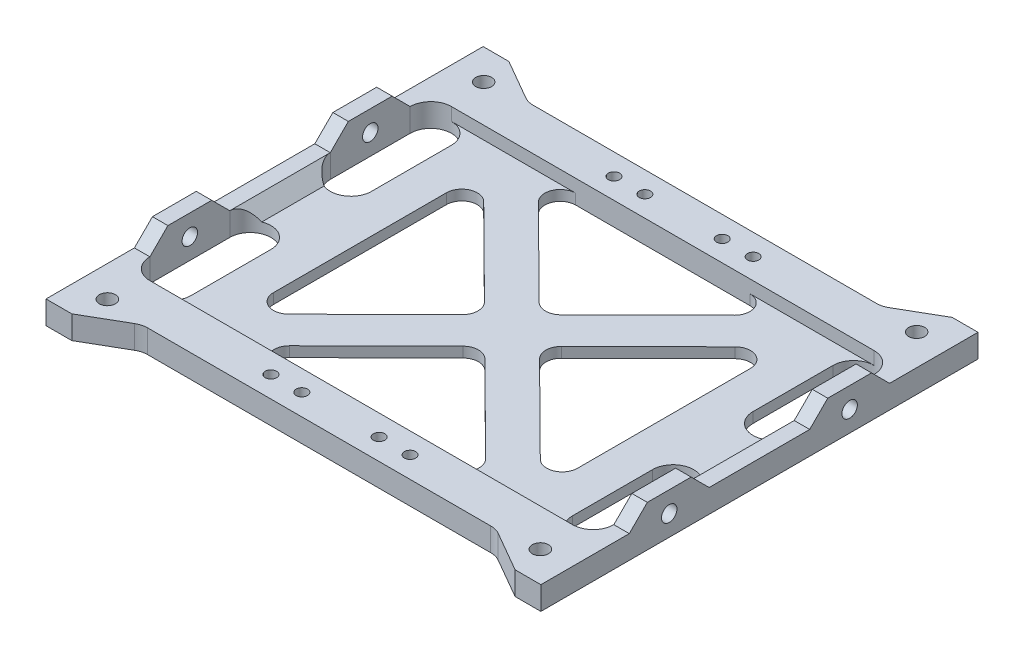
SolidWorks part; units mm, degrees
material "6061-T6 (SS)"
ref_plane "Front Plane" through (0, 0, 0) normal (0, 0, 1) x (1, 0, 0)
ref_plane "Top Plane" through (0, 0, 0) normal (0, 1, 0) x (1, 0, 0)
ref_plane "Right Plane" through (0, 0, 0) normal (1, 0, 0) x (0, 0, -1)
sketch "Sketch1" plane through (0, 0, 0) normal (0, 1, 0) x (1, 0, 0)
  line L0 (-41, 25.25) -> (-41, 9.75) construction
  line L1 (-48, -42.4) -> (-43, -42.4)
  line L2 (-48, -42.4) -> (-48, 42.4)
  line L3 (-48, 42.4) -> (-43, 42.4)
  line L4 (48, -42.4) -> (48, 42.4)
  line L5 (-48, -42.4) -> (48, 42.4) construction
  line L6 (-48, 42.4) -> (48, -42.4) construction
  line L7 (-37, 25.25) -> (-37, 9.75)
  line L8 (-45, 25.25) -> (-45, 9.75)
  line L9 (-41, -9.75) -> (-41, -25.25) construction
  line L10 (-37, -9.75) -> (-37, -25.25)
  line L11 (-45, -9.75) -> (-45, -25.25)
  line L12 (41, 25.25) -> (41, 9.75) construction
  line L13 (45, 25.25) -> (45, 9.75)
  line L14 (37, 25.25) -> (37, 9.75)
  line L15 (41, -9.75) -> (41, -25.25) construction
  line L16 (45, -9.75) -> (45, -25.25)
  line L17 (37, -9.75) -> (37, -25.25)
  line L18 (-43, -42.4) -> (-35.2679, -37.9359)
  line L19 (-33.2679, -37.4) -> (33.2679, -37.4)
  line L20 (35.2679, -37.9359) -> (43, -42.4)
  line L21 (43, 42.4) -> (35.2679, 37.9359)
  line L22 (33.2679, 37.4) -> (-33.2679, 37.4)
  line L23 (-35.2679, 37.9359) -> (-43, 42.4)
  line L24 (43, -42.4) -> (48, -42.4)
  line L25 (43, 42.4) -> (48, 42.4)
  line L26 (-37.6698, 33.275) -> (37.6698, 33.275) construction
  line L27 (37.6698, -33.275) -> (-37.6698, -33.275) construction
  line L29 (-42, 36.5) -> (42, 36.5) construction
  line L30 (-42, 36.5) -> (-42, -36.5) construction
  line L31 (-42, -36.5) -> (42, -36.5) construction
  line L32 (42, 36.5) -> (42, -36.5) construction
  line L33 (-42, 36.5) -> (42, -36.5) construction
  line L34 (-42, -36.5) -> (42, 36.5) construction
  arc A0 (-37, 25.25) -> (-45, 25.25) centre (-41, 25.25) ccw
  arc A1 (-45, 9.75) -> (-37, 9.75) centre (-41, 9.75) ccw
  arc A2 (-37, -9.75) -> (-45, -9.75) centre (-41, -9.75) ccw
  arc A3 (-45, -25.25) -> (-37, -25.25) centre (-41, -25.25) ccw
  arc A4 (45, 25.25) -> (37, 25.25) centre (41, 25.25) ccw
  arc A5 (37, 9.75) -> (45, 9.75) centre (41, 9.75) ccw
  arc A6 (45, -9.75) -> (37, -9.75) centre (41, -9.75) ccw
  arc A7 (37, -25.25) -> (45, -25.25) centre (41, -25.25) ccw
  arc A8 (35.2679, -37.9359) -> (33.2679, -37.4) centre (33.2679, -41.4) ccw
  arc A9 (-33.2679, -37.4) -> (-35.2679, -37.9359) centre (-33.2679, -41.4) ccw
  arc A10 (35.2679, 37.9359) -> (33.2679, 37.4) centre (33.2679, 41.4) cw
  arc A11 (-33.2679, 37.4) -> (-35.2679, 37.9359) centre (-33.2679, 41.4) cw
  circle A12 centre (-13.5, -33.275) radius 1.1
  circle A13 centre (-7.5, -33.275) radius 1.1
  circle A14 centre (7.5, -33.275) radius 1.1
  circle A15 centre (13.5, -33.275) radius 1.1
  circle A16 centre (-13.5, 33.275) radius 1.1
  circle A17 centre (-7.5, 33.275) radius 1.1
  circle A18 centre (7.5, 33.275) radius 1.1
  circle A19 centre (13.5, 33.275) radius 1.1
  circle A20 centre (-42, 36.5) radius 1.55
  circle A21 centre (42, 36.5) radius 1.55
  circle A22 centre (42, -36.5) radius 1.55
  circle A23 centre (-42, -36.5) radius 1.55
  point P0 (0, 0)
  point P8 (-41, 17.5)
  point P13 (-41, -17.5)
  point P20 (41, 17.5)
  point P27 (41, -17.5)
  point P44 (34.3397, -37.4)
  point P47 (-34.3397, -37.4)
  point P76 (0, 0)
  dimension "D3" = 4
  dimension "D15" = 4
  dimension "D21" = 2.2
  dimension "D31" = 3.1
  dimension "D1" = 96
  dimension "D2" = 84.8
  dimension "D4" = 35
  dimension "D5" = 24.9
  dimension "D6" = 35
  dimension "D7" = 24.9
  dimension "D8" = 15.5
  dimension "D9" = 3
  dimension "D10" = 3
  dimension "D11" = 5
  dimension "D13" = 30
  dimension "D14" = 30
  dimension "D17" = 30
  dimension "D18" = 30
  dimension "D19" = 5
  dimension "D20" = 4.125
  dimension "D22" = 15
  dimension "D23" = 7.5
  dimension "D24" = 6
  dimension "D25" = 6
  dimension "D26" = 15
  dimension "D27" = 7.5
  dimension "D28" = 6
  dimension "D29" = 6
  dimension "D12" = 5
  dimension "D16" = 5
  dimension "69" = 73
  dimension "D30" = 84
extrude "Boss-Extrude1" add sketch "Sketch1" along normal blind 2
sketch "Sketch2" plane through (0, 2, 0) normal (0, 1, 0) x (1, 0, 0)
  line L0 (37, -9.75) -> (37, -25.25) construction
  line L1 (37, 25.25) -> (37, 9.75) construction
  line L2 (-45, 25.25) -> (-45, 9.75) construction
  line L3 (-45, -9.75) -> (-45, -25.25) construction
  line L4 (37, -9.75) -> (37, -25.25)
  line L5 (37, 25.25) -> (37, 9.75)
  line L6 (-45, 25.25) -> (-45, 9.75)
  line L7 (-45, -9.75) -> (-45, -25.25)
  line L8 (-45, 9.75) -> (-45, -9.75)
  line L10 (-41, 29.25) -> (41, 29.25)
  line L13 (41, -29.25) -> (-41, -29.25)
  line L15 (45, 25.25) -> (45, -25.25)
  line L17 (-33.2679, -37.4) -> (33.2679, -37.4) construction
  line L18 (48, 42.4) -> (43, 42.4) construction
  line L19 (43, 42.4) -> (35.2679, 37.9359) construction
  line L20 (33.2679, 37.4) -> (-33.2679, 37.4) construction
  line L21 (-35.2679, 37.9359) -> (-43, 42.4) construction
  line L22 (-43, 42.4) -> (-48, 42.4) construction
  line L23 (-48, 42.4) -> (-48, -42.4) construction
  line L24 (-48, -42.4) -> (-43, -42.4) construction
  line L25 (-43, -42.4) -> (-35.2679, -37.9359) construction
  line L26 (48, -42.4) -> (48, 42.4) construction
  line L27 (43, -42.4) -> (48, -42.4) construction
  line L28 (35.2679, -37.9359) -> (43, -42.4) construction
  line L29 (48, 42.4) -> (43, 42.4)
  line L30 (43, 42.4) -> (35.2679, 37.9359)
  line L31 (33.2679, 37.4) -> (-33.2679, 37.4)
  line L32 (-35.2679, 37.9359) -> (-43, 42.4)
  line L33 (-43, 42.4) -> (-48, 42.4)
  line L34 (-48, 42.4) -> (-48, -42.4)
  line L35 (-48, -42.4) -> (-43, -42.4)
  line L36 (-43, -42.4) -> (-35.2679, -37.9359)
  line L37 (48, -42.4) -> (48, 42.4)
  line L38 (43, -42.4) -> (48, -42.4)
  line L39 (35.2679, -37.9359) -> (43, -42.4)
  line L40 (-33.2679, -37.4) -> (33.2679, -37.4)
  arc A0 (-45, -25.25) -> (-37, -25.25) centre (-41, -25.25) ccw construction
  arc A1 (37, -25.25) -> (45, -25.25) centre (41, -25.25) ccw construction
  arc A2 (45, 25.25) -> (37, 25.25) centre (41, 25.25) ccw construction
  arc A3 (-37, 25.25) -> (-45, 25.25) centre (-41, 25.25) ccw construction
  arc A4 (-45, -25.25) -> (-37, -25.25) centre (-41, -25.25) ccw
  arc A5 (37, -25.25) -> (45, -25.25) centre (41, -25.25) ccw
  arc A6 (45, 25.25) -> (37, 25.25) centre (41, 25.25) ccw
  arc A7 (-37, 25.25) -> (-45, 25.25) centre (-41, 25.25) ccw
  arc A8 (33.2679, 37.4) -> (35.2679, 37.9359) centre (33.2679, 41.4) ccw construction
  arc A9 (-35.2679, 37.9359) -> (-33.2679, 37.4) centre (-33.2679, 41.4) ccw construction
  arc A10 (35.2679, -37.9359) -> (33.2679, -37.4) centre (33.2679, -41.4) ccw construction
  arc A11 (33.2679, 37.4) -> (35.2679, 37.9359) centre (33.2679, 41.4) ccw
  arc A12 (-35.2679, 37.9359) -> (-33.2679, 37.4) centre (-33.2679, 41.4) ccw
  arc A13 (35.2679, -37.9359) -> (33.2679, -37.4) centre (33.2679, -41.4) ccw
  arc A14 (-33.2679, -37.4) -> (-35.2679, -37.9359) centre (-33.2679, -41.4) ccw construction
  arc A15 (-33.2679, -37.4) -> (-35.2679, -37.9359) centre (-33.2679, -41.4) ccw
  point P60 (0, 0)
extrude "Boss-Extrude2" add sketch "Sketch2" along normal blind 2.5
sketch "Sketch3" plane through (48, 0, 0) normal (1, 0, 0) x (0, 0, -1)
  line L0 (-42.4, 4.5) -> (42.4, 4.5) construction
  line L1 (-42.4, 4.5) -> (42.4, 4.5)
  line L3 (-25.25, 4.5) -> (-9.75, 4.5)
  line L4 (-25.25, 4.5) -> (-25.25, 8)
  line L5 (-25.25, 8) -> (-9.75, 8)
  line L6 (-9.75, 4.5) -> (-9.75, 8)
  line L7 (9.75, 4.5) -> (25.25, 4.5)
  line L8 (9.75, 4.5) -> (9.75, 8)
  line L9 (9.75, 8) -> (25.25, 8)
  line L10 (25.25, 4.5) -> (25.25, 8)
  line L18 (9.75, 0) -> (25.25, 0)
  line L19 (9.75, 2) -> (9.75, 0)
  line L20 (-9.75, 2) -> (9.75, 2)
  line L21 (-9.75, 0) -> (-9.75, 2)
  line L22 (-25.25, 0) -> (-9.75, 0)
  line L23 (-25.25, 4.5) -> (-25.25, 0)
  line L24 (25.25, 4.5) -> (-25.25, 4.5)
  line L25 (25.25, 0) -> (25.25, 4.5)
  line L26 (9.75, 0) -> (25.25, 0) construction
  line L27 (9.75, 2) -> (9.75, 0) construction
  line L28 (-9.75, 2) -> (9.75, 2) construction
  line L29 (-9.75, 0) -> (-9.75, 2) construction
  line L30 (-25.25, 0) -> (-9.75, 0) construction
  line L31 (-25.25, 4.5) -> (-25.25, 0) construction
  line L32 (25.25, 4.5) -> (-25.25, 4.5)
  line L33 (25.25, 0) -> (25.25, 4.5)
  dimension "D2" = 8
  dimension "D1" = 0
extrude "Boss-Extrude3" add sketch "Sketch3" against normal up to vertex (2.5 mm away) contours L1 L6 L5 L4 | L1 L10 L9 L8
sketch "Sketch4" plane through (48, 0, 0) normal (1, 0, 0) x (0, 0, -1)
  line L0 (-25.25, 8) -> (-25.25, 0) construction
  line L1 (-42.4, 0) -> (42.4, 0) construction
  line L2 (-25.25, 4) -> (17.5, 4) construction
  line L3 (-9.75, 4.5) -> (9.75, 4.5) construction
  line L4 (-17.5, 8) -> (-17.5, 0) construction
  line L5 (-25.25, 8) -> (-9.75, 8) construction
  line L7 (17.5, 8) -> (17.5, 0) construction
  line L8 (9.75, 8) -> (25.25, 8) construction
  circle A0 centre (-17.5, 4) radius 1.5
  circle A1 centre (17.5, 4) radius 1.5
  dimension "D1" = 3
extrude "Cut-Extrude1" cut sketch "Sketch4" against normal blind 5
mirror "Mirror1" about plane through (0, 0, 0) normal (1, 0, 0) of "Cut-Extrude1", "Boss-Extrude3"
sketch "Sketch5" plane through (0, 2, 0) normal (0, 1, 0) x (1, 0, 0)
  line L0 (-41, 29.25) -> (41, 29.25) construction
  line L1 (-29.5, -29.25) -> (29.5, -29.25) construction
  line L2 (-29.5, -29.25) -> (-29.5, 29.25) construction
  line L3 (-29.5, 29.25) -> (29.5, 29.25) construction
  line L4 (29.5, -29.25) -> (29.5, 29.25) construction
  line L5 (41, -29.25) -> (-41, -29.25) construction
  line L6 (-37, 9.75) -> (-37, 25.25) construction
  line L7 (37, 25.25) -> (37, 9.75) construction
  line L8 (-29.5, -29.25) -> (29.5, 29.25) construction
  line L9 (29.5, -29.25) -> (-29.5, 29.25) construction
  line L10 (-24.3877, -18.9002) -> (-7.4745, -2.1303)
  line L11 (-7.4745, 2.1303) -> (-24.3877, 18.9002)
  line L12 (-29.5, 16.7698) -> (-29.5, -16.7698)
  line L19 (18.9998, 24.1197) -> (2.1123, 7.3753)
  line L20 (-2.1123, 7.3753) -> (-18.9998, 24.1197)
  line L21 (-16.8875, 29.25) -> (16.8875, 29.25)
  line L22 (-18.9998, -24.1197) -> (-2.1123, -7.3753)
  line L23 (2.1123, -7.3753) -> (18.9998, -24.1197)
  line L24 (16.8875, -29.25) -> (-16.8875, -29.25)
  line L25 (7.4745, 2.1303) -> (24.3877, 18.9002)
  line L26 (29.5, 16.7698) -> (29.5, -16.7698)
  line L27 (24.3877, -18.9002) -> (7.4745, -2.1303)
  arc A0 (-18.9998, -24.1197) -> (-16.8875, -29.25) centre (-16.8875, -26.25) ccw
  arc A1 (16.8875, -29.25) -> (18.9998, -24.1197) centre (16.8875, -26.25) ccw
  arc A2 (29.5, -16.7698) -> (24.3877, -18.9002) centre (26.5, -16.7698) cw
  arc A3 (29.5, 16.7698) -> (24.3877, 18.9002) centre (26.5, 16.7698) ccw
  arc A4 (18.9998, 24.1197) -> (16.8875, 29.25) centre (16.8875, 26.25) ccw
  arc A5 (-16.8875, 29.25) -> (-18.9998, 24.1197) centre (-16.8875, 26.25) ccw
  arc A6 (-24.3877, 18.9002) -> (-29.5, 16.7698) centre (-26.5, 16.7698) ccw
  arc A7 (-29.5, -16.7698) -> (-24.3877, -18.9002) centre (-26.5, -16.7698) ccw
  arc A8 (-2.1123, -7.3753) -> (2.1123, -7.3753) centre (0, -9.5056) cw
  arc A9 (7.4745, -2.1303) -> (7.4745, 2.1303) centre (9.5868, 0) cw
  arc A10 (2.1123, 7.3753) -> (-2.1123, 7.3753) centre (0, 9.5056) cw
  arc A11 (-7.4745, 2.1303) -> (-7.4745, -2.1303) centre (-9.5868, 0) cw
  point P26 (-24.174, -29.25)
  point P29 (24.174, -29.25)
  point P32 (29.5, -23.9691)
  point P35 (29.5, 23.9691)
  point P38 (24.174, 29.25)
  point P41 (-24.174, 29.25)
  point P44 (-29.5, 23.9691)
  point P47 (-29.5, -23.9691)
  dimension "D5" = 3
  dimension "D1" = 7.5
  dimension "D2" = 7.5
  dimension "D3" = 7.5
  dimension "D4" = 7.5
extrude "Cut-Extrude2" cut sketch "Sketch5" against normal through all
sketch "Sketch6" plane through (-48, 0, 0) normal (-1, 0, 0) x (0, 0, 1)
  line L0 (-25.25, 4.5) -> (-21.75, 8)
  line L1 (-9.75, 8) -> (-25.25, 8) construction
  line L2 (-9.75, 4.5) -> (-13.25, 8)
  line L3 (-13.25, 8) -> (-9.75, 8)
  line L4 (-9.75, 8) -> (-9.75, 4.5)
  line L5 (-21.75, 8) -> (-25.25, 8)
  line L6 (-25.25, 8) -> (-25.25, 4.5)
  line L7 (9.75, 4.5) -> (9.75, 8)
  line L8 (9.75, 8) -> (13.25, 8)
  line L9 (25.25, 8) -> (9.75, 8) construction
  line L10 (13.25, 8) -> (9.75, 4.5)
  line L11 (25.25, 4.5) -> (25.25, 8)
  line L12 (25.25, 8) -> (21.75, 8)
  line L13 (21.75, 8) -> (25.25, 4.5)
  dimension "D1" = 45
extrude "Cut-Extrude3" cut sketch "Sketch6" against normal through all
chamfer "Chamfer1" distance 2.5 angle 45 2 edges at (-45, 2, 0) (45, 2, 0)
sketch "Sketch7" plane through (0, 4.5, 0) normal (0, 1, 0) x (1, 0, 0)
  line L0 (-48, 42.4) -> (-48, 25.25) construction
  line L1 (-43, 42.4) -> (-48, 42.4) construction
  line L2 (-35.2679, 37.9359) -> (-43, 42.4) construction
  line L3 (-48, 42.4) -> (-48, 25.25)
  line L4 (-43, 42.4) -> (-48, 42.4)
  line L5 (-35.2679, 37.9359) -> (-43, 42.4)
  line L6 (-46.6095, 36.5) -> (-46.6095, 30.6032)
  line L7 (-48, -25.25) -> (-48, -42.4) construction
  line L8 (-48, -42.4) -> (-43, -42.4) construction
  line L9 (-43, -42.4) -> (-35.2679, -37.9359) construction
  line L10 (-48, -25.25) -> (-48, -42.4)
  line L11 (-48, -42.4) -> (-43, -42.4)
  line L12 (-43, -42.4) -> (-35.2679, -37.9359)
  line L13 (-46.6095, -36.5) -> (-46.6095, -30.6032)
  arc A0 (-39.6952, 40.492) -> (-46.6095, 36.5) centre (-42, 36.5) ccw
  arc A1 (-47.1152, 28.6566) -> (-48, 25.25) centre (-41, 25.25) ccw
  arc A2 (-46.6095, 30.6032) -> (-47.1152, 28.6566) centre (-50.6095, 30.6032) cw
  arc A3 (-46.6095, -36.5) -> (-39.6952, -40.492) centre (-42, -36.5) ccw
  arc A4 (-48, -25.25) -> (-47.1152, -28.6566) centre (-41, -25.25) ccw
  arc A5 (-47.1152, -28.6566) -> (-46.6095, -30.6032) centre (-50.6095, -30.6032) cw
  line M10 (-48, 42.4) -> (-48, 25.25)
  line M23 (-43, 42.4) -> (-48, 42.4)
  dimension "D1" = 4
  dimension "D2" = 4
extrude "Cut-Extrude4" [suppressed] cut sketch "Sketch7" against normal through all contours A5 A4 L10 L11 L12 A3 L13 | A2 L6 A0 L5 A1 M23 M10
mirror "Mirror2" [suppressed] about plane through (0, 0, 0) normal (1, 0, 0)
equation "\"D5@Sketch1\"=(\"D2@Sketch1\"-\"D4@Sketch1\")/2"
equation "\"D6@Sketch1\"=\"D4@Sketch1\""
equation "\"D7@Sketch1\"=\"D5@Sketch1\""
equation "\"D10@Sketch1\"=\"D9@Sketch1\""
equation "\"D19@Sketch1\"=\"D11@Sketch1\""
equation "\"D18@Sketch1\"=\"D17@Sketch1\""
equation "\"D13@Sketch1\"=\"D17@Sketch1\""
equation "\"D14@Sketch1\"=\"D17@Sketch1\""
equation "\"D23@Sketch1\"=\"D22@Sketch1\"/2"
equation "\"D25@Sketch1\"=\"D24@Sketch1\""
equation "\"D26@Sketch1\"=\"D22@Sketch1\""
equation "\"D27@Sketch1\"=\"D23@Sketch1\""
equation "\"D28@Sketch1\"=\"D24@Sketch1\""
equation "\"D29@Sketch1\"=\"D28@Sketch1\""
equation "\"D2@Sketch5\"=\"D1@Sketch5\""
equation "\"D4@Sketch5\"=\"D3@Sketch5\""
equation "\"D20@Sketch1\"=8.25/2"
